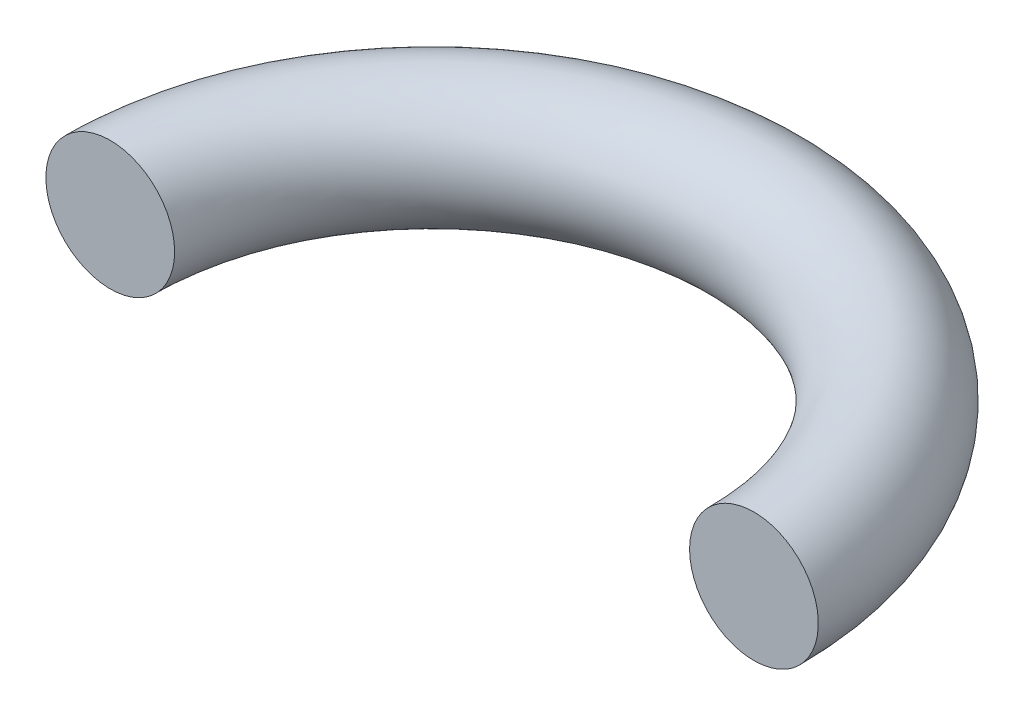
SolidWorks part; units mm, degrees
material "steel"
ref_plane "Przednia" through (0, 0, 0) normal (0, 0, 1) x (1, 0, 0)
ref_plane "Górna" through (0, 0, 0) normal (0, 1, 0) x (1, 0, 0)
ref_plane "Prawa" through (0, 0, 0) normal (1, 0, 0) x (0, 0, -1)
sketch "Sketch1" plane through (0, 0, 0) normal (0, 1, 0) x (1, 0, 0)
  arc A0 (5, 0) -> (-5, 0) centre (0, 0) ccw
  dimension "D1" = 5
sketch "Sketch2" plane through (0, 0, 0) normal (0, 0, 1) x (1, 0, 0)
  circle A0 centre (-5, 0) radius 1
  dimension "D1" = 2
sweep "Sweep1" add profiles "Sketch2" path "Sketch1"
ref_axis "Axis1" through (-5, 0, 0) along (0, 0, 1)
ref_axis "Axis2" through (5, 0, 0) along (0, 0, 1)
ref_plane "Plane1" through (0, 0, 0) normal (0, 1, 0) x (1, 0, 0)
